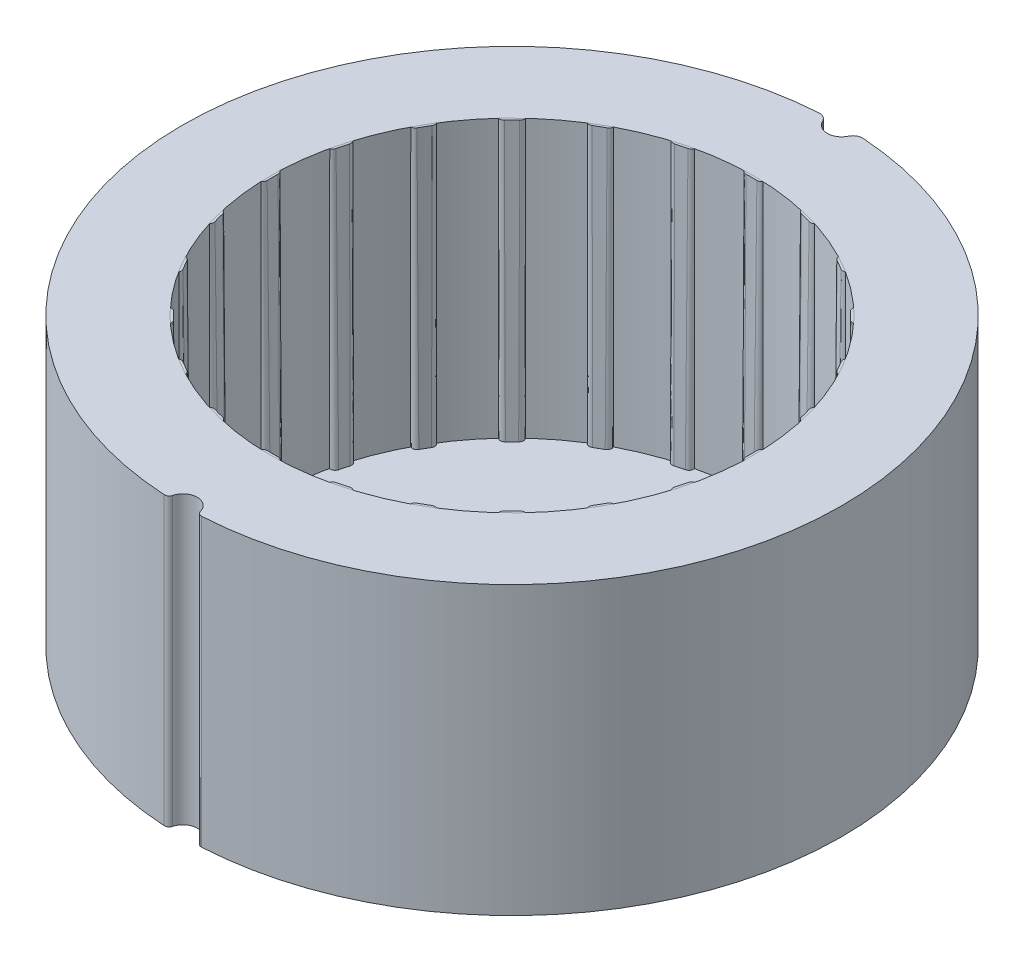
SolidWorks part; units mm, degrees
other "Markup1"
sketch "Sketch4"
other "Markup5"
sketch "Sketch8" plane through (34.5, 25, 34.4428) normal (0.0041, 0.9851, 0.1719) x (0.981, -0.0374, 0.1906)
other "Markup6"
sketch "Sketch9" plane through (34.5, 25, 34.4428) normal (0.0041, 0.9851, 0.1719) x (0.981, -0.0374, 0.1906)
other "Markup7"
sketch "Sketch10" plane through (-34.5, 25, 34.4428) normal (-0.125, 0.9874, 0.0969) x (0.5933, -0.0039, 0.805)
ref_plane "Front Plane" through (0, 0, 0) normal (0, 0, 1) x (1, 0, 0)
ref_plane "Top Plane" through (0, 0, 0) normal (0, 1, 0) x (1, 0, 0)
ref_plane "Right Plane" through (0, 0, 0) normal (1, 0, 0) x (0, 0, -1)
sketch "Sketch1" plane through (0, 0, 0) normal (0, 1, 0) x (1, 0, 0)
  line L3 (0, 0.002) -> (0, 3.7877) construction
  line L4 (0, 3.7877) -> (2.417, 3.7877)
  line L5 (0, 3.7877) -> (-2.417, 3.7877)
  arc A0 (1.9642, -34.442) -> (34.1982, 4.5552) centre (0, 0.002) ccw
  arc A2 (-2.417, 3.7877) -> (2.417, 3.7877) centre (0, 0.002) ccw
  circle A3 centre (0, 0.002) radius 34.5 construction
  arc A7 (-1.3541, 33.8562) -> (1.3541, 33.8562) centre (0, 34.5015) ccw
  arc A8 (34.1982, 4.5552) -> (2.3241, 34.4236) centre (0, 0.002) ccw
  arc A9 (-2.3241, 34.4236) -> (-34.1982, 4.5552) centre (0, 0.002) ccw
  arc A10 (-34.1982, 4.5552) -> (-1.9642, -34.442) centre (0, 0.002) ccw
  arc A11 (1.3541, 33.8562) -> (2.3241, 34.4236) centre (2.2568, 33.4259) cw
  arc A12 (-1.3541, 33.8562) -> (-2.3241, 34.4236) centre (-2.2568, 33.4259) ccw
  arc A13 (1.4518, -34.0686) -> (-1.4518, -34.0686) centre (0, -34.4457) ccw
  arc A14 (1.4518, -34.0686) -> (1.9642, -34.442) centre (1.9358, -33.9428) ccw
  arc A15 (-1.4518, -34.0686) -> (-1.9642, -34.442) centre (-1.9358, -33.9428) cw
  point P15 (1.4997, 34.4694)
  dimension "D2" = 4.834
  dimension "D3" = 4.4915
  dimension "D4" = 34.5
  dimension "D5" = 1
  dimension "D6" = 1.5
  dimension "D7" = 0.5
  dimension "D11" = 1.4997
sketch "Sketch2" plane through (0, 0, 0) normal (0, 1, 0) x (1, 0, 0)
  line L0 (0, 25.3) -> (0, 24.8) construction
  line L1 (-0.9998, 25.2802) -> (0, 25.3) construction
  line L2 (0, 25.3) -> (0.9998, 25.2802) construction
  line L3 (-0.9998, 25.2802) -> (-0.9998, 24.7798)
  line L6 (0.9998, 24.7798) -> (0.9998, 25.2802)
  circle A16 centre (0, 0) radius 25.3
  arc A18 (-0.9998, 24.7798) -> (0.9998, 24.7798) centre (0, 0) cw
  point P3 (0, 24.8)
  dimension "D1" = 50.6
  dimension "D2" = 1
  dimension "D3" = 0.5
extrude "Boss-Extrude1" add sketch "Sketch1" along normal blind 30 contours A10 A0 A8 A7 A9 A2 L5 L4 | L5 A2 L4 region at (0, 0, 0.1522) region at (2.2155, 0, 33.5591)
extrude "Cut-Extrude2" cut sketch "Sketch2" along normal up to next from offset 1 contours A16 | A16 region at (0, 0, 0.0125)
extrude "Boss-Extrude2" add sketch "Sketch2<2>" along normal up to surface (30 mm away) separate body contours A16 region at (0, 0, -25.0433) up to face at (0, 30, 25.3)
sketch "Sketch2<2>" plane through (0, 0, 0) normal (0, 1, 0) x (1, 0, 0) same geometry as "Sketch2"
draft "Draft1" type of draft neutral plane draft angle 0.5 neutral plane "Top Plane" faces to draft 1 face at (0, 15, -24.7899) neutral plane through (0, 0, 0) neutral plane normal (0, 1, 0) parameters "D1"=0.5
fillet "Fillet1" radius 0.5 2 edges
pattern_circular "CirPattern2" count 24 over 360 about axis through (0, 30, 0) along (0, 1, 0) of bodies 106
